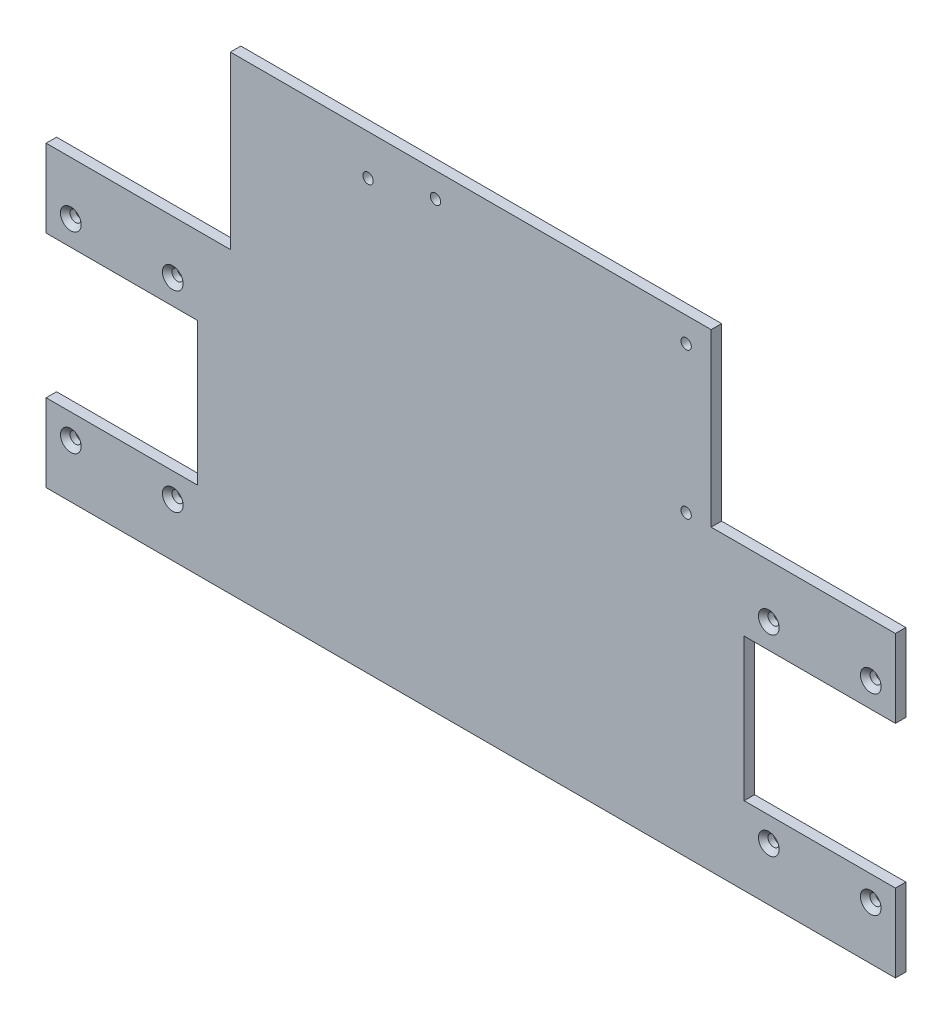
SolidWorks part; units mm, degrees
ref_plane "Top Plane" through (0, 0, 0) normal (0, 0, 1) x (1, 0, 0)
ref_plane "Front Plane" through (0, 0, 0) normal (0, 1, 0) x (1, 0, 0)
ref_plane "Right Plane" through (0, 0, 0) normal (1, 0, 0) x (0, 0, -1)
sketch "Profile Sketch" plane through (0, 0, 0) normal (0, 0, 1) x (1, 0, 0)
  line L0 (73.09, 45.35) -> (129.1, 45.35)
  line L1 (-129.1, -45.35) -> (129.1, -45.35)
  line L2 (-129.1, -45.35) -> (-129.1, 45.35)
  line L3 (-129.1, 45.35) -> (-73.09, 45.35)
  line L4 (129.1, -45.35) -> (129.1, 45.35)
  line L5 (-129.1, -45.35) -> (129.1, 45.35) construction
  line L6 (-129.1, 45.35) -> (129.1, -45.35) construction
  line L7 (-73.09, 97.35) -> (73.09, 97.35)
  line L8 (-73.09, 97.35) -> (-73.09, 45.35)
  line L10 (73.09, 97.35) -> (73.09, 45.35)
  line L11 (-73.09, 97.35) -> (73.09, 45.35) construction
  line L12 (-73.09, 45.35) -> (73.09, 97.35) construction
  point P0 (0, 0)
  point P6 (0, 71.35)
  dimension "D1" = 90.7
  dimension "D2" = 258.2
  dimension "D3" = 52
  dimension "D4" = 146.18
extrude "Profile Extrude" add sketch "Profile Sketch" along normal blind 3.175
sketch "Film Feeder Mounting Hole Sketch" plane through (0, 0, 3.175) normal (0, 0, 1) x (1, 0, 0)
  line L0 (0, 97.35) -> (0, -45.35) construction
  line L2 (-129.1, -45.35) -> (129.1, -45.35) construction
  line L3 (-129.1, 0) -> (129.1, 0) construction
  line L4 (-129.1, 45.35) -> (-129.1, -45.35) construction
  line L5 (129.1, -45.35) -> (129.1, 45.35) construction
  line L6 (-106.1, 29.175) -> (-106.1, -29.175) construction
  line L7 (73.09, 97.35) -> (-73.09, 97.35) construction
  point P0 (-121.6, 29.175)
  point P1 (-121.6, -29.175)
  point P2 (-90.6, -29.175)
  point P3 (-90.6, 29.175)
  point P18 (90.6, 29.175)
  point P19 (121.6, 29.175)
  point P20 (90.6, -29.175)
  point P21 (121.6, -29.175)
  dimension "D1" = 31
  dimension "D2" = 58.35
  dimension "D3" = 7.5
hole_wizard "CSK for M3 Flat Head Machine Screw1" positions "3DSketch1" profile "Sketch2" countersink size "M3" standard "ANSI Metric" end condition through all
sketch3d "3DSketch1"
  point P0 (-121.6, 29.175, 3.175)
  point P3 (-90.6, 29.175, 3.175)
  point P6 (-90.6, -29.175, 3.175)
  point P9 (-121.6, -29.175, 3.175)
  point P13 (90.6, 29.175, 3.175)
  point P16 (121.6, 29.175, 3.175)
  point P19 (121.6, -29.175, 3.175)
  point P22 (90.6, -29.175, 3.175)
sketch "Sketch2" plane through (-121.6, 29.175, 3.175) normal (1, 0, 0) x (0, -1, 0)
  line L0 (0, 0) -> (0, 3.175)
  line L1 (0, 3.175) -> (1.7, 3.175)
  line L2 (1.7, 3.175) -> (1.7, 1.45)
  line L3 (1.7, 1.45) -> (3.15, 0)
  line L5 (3.15, 0) -> (0, 0)
  line L6 (-1.7, 1.45) -> (-3.15, 0) construction
  line L11 (0, -6.35) -> (0, 107.95) construction
  dimension "Thru Hole Dia." = 3.4
  dimension "Thru Hole Depth" = 3.175
  dimension "Near C'Sink Dia." = 6.3
  dimension "Near C'Sink Angle" = 90
sketch "Film Feeder Clearance Sketch" plane through (0, 0, 3.175) normal (0, 0, 1) x (1, 0, 0)
  line L0 (-129.1, 45.35) -> (-129.1, -45.35) construction
  line L1 (-129.1, 21.675) -> (-83.1, 21.675)
  line L2 (-129.1, 21.675) -> (-129.1, -21.675)
  line L3 (-129.1, -21.675) -> (-83.1, -21.675)
  line L4 (-83.1, 21.675) -> (-83.1, -21.675)
  line L5 (-129.1, 21.675) -> (-83.1, -21.675) construction
  line L6 (-129.1, -21.675) -> (-83.1, 21.675) construction
  line L7 (129.1, -45.35) -> (129.1, 45.35) construction
  line L8 (83.1, -21.675) -> (129.1, -21.675)
  line L9 (83.1, -21.675) -> (83.1, 21.675)
  line L10 (83.1, 21.675) -> (129.1, 21.675)
  line L11 (129.1, -21.675) -> (129.1, 21.675)
  line L12 (83.1, -21.675) -> (129.1, 21.675) construction
  line L13 (83.1, 21.675) -> (129.1, -21.675) construction
  point P0 (-106.1, 0)
  point P8 (106.1, 0)
  dimension "D1" = 46
  dimension "D2" = 43.35
  dimension "D3" = 46
  dimension "D4" = 43.35
extrude "Film Feeder Clearance Cut" cut sketch "Film Feeder Clearance Sketch" against normal through all
sketch "Gantry Mounting Hole Sketch" plane through (0, 0, 3.175) normal (0, 0, 1) x (1, 0, 0)
  line L0 (73.09, 97.35) -> (-73.09, 97.35) construction
  line L1 (73.09, 45.35) -> (73.09, 97.35) construction
  circle A0 centre (-10.73, 89.85) radius 1.575
  circle A1 centre (65.47, 89.85) radius 1.575
  circle A2 centre (65.47, 45.35) radius 1.575
  dimension "D2" = 3.15
  dimension "D4" = 3.15
  dimension "D7" = 3.15
  dimension "D1" = 7.5
  dimension "D3" = 76.2
  dimension "D5" = 7.5
  dimension "D6" = 7.62
  dimension "D9" = 44.5
extrude "Gantry Mounting Hole Cut" cut sketch "Gantry Mounting Hole Sketch" against normal through all
sketch "Eraser Mounting Hole Sketch" plane through (0, 0, 3.175) normal (0, 0, 1) x (1, 0, 0)
  line L0 (73.09, 97.35) -> (-73.09, 97.35) construction
  circle A0 centre (-31.23, 85.05) radius 1.575
  circle A2 centre (-10.73, 89.85) radius 1.575 construction
  dimension "D1" = 3.15
  dimension "D3" = 20.5
  dimension "D2" = 12.3
extrude "Eraser Mounting Hole Cut" cut sketch "Eraser Mounting Hole Sketch" against normal through all
equation "\"D3@Film Feeder Clearance Sketch\"=\"D1@Film Feeder Clearance Sketch\""
equation "\"D4@Film Feeder Clearance Sketch\"=\"D2@Film Feeder Clearance Sketch\""
equation "\"D4@Gantry Mounting Hole Sketch\"=\"D2@Gantry Mounting Hole Sketch\""
equation "\"D5@Gantry Mounting Hole Sketch\"=\"D1@Gantry Mounting Hole Sketch\""
